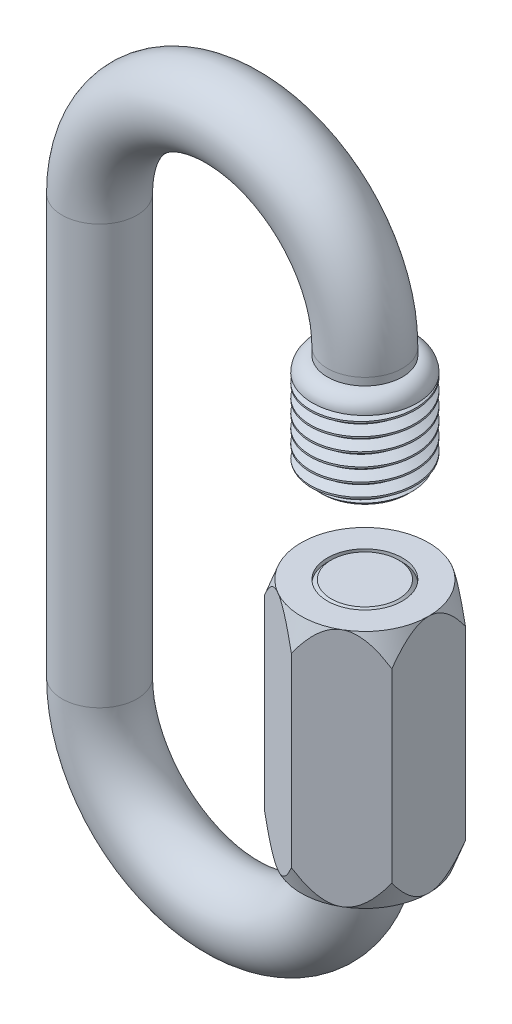
SolidWorks part; units mm, degrees
ref_plane "Front Plane" through (0, 0, 0) normal (0, 0, 1) x (1, 0, 0)
ref_plane "Top Plane" through (0, 0, 0) normal (0, 1, 0) x (1, 0, 0)
ref_plane "Right Plane" through (0, 0, 0) normal (1, 0, 0) x (0, 0, -1)
sketch "Sketch1" plane through (0, 0, 0) normal (0, 0, 1) x (1, 0, 0)
  line L0 (6.35, 13.97) -> (6.35, 13.47) construction
  line L1 (-11.35, 25.32) -> (11.35, 25.32) construction
  line L2 (-11.35, 25.32) -> (-11.35, -25.32) construction
  line L3 (-11.35, -25.32) -> (11.35, -25.32) construction
  line L4 (11.35, 25.32) -> (11.35, 13.97) construction
  line L5 (4.6, 0.53) -> (13.1, 0.53) construction
  line L6 (4.6, 0.53) -> (4.6, -15.47) construction
  line L7 (4.6, -15.47) -> (13.1, -15.47) construction
  line L8 (13.1, 0.53) -> (13.1, -15.47) construction
  line L9 (-11.35, 0) -> (-6.35, 0) construction
  line L10 (-6.35, -13.97) -> (-6.35, 13.97) construction
  line L11 (6.35, 0.53) -> (6.35, -13.97) construction
  line L12 (6.35, -13.97) -> (11.35, -13.97) construction
  line L13 (11.35, 0.53) -> (11.35, -25.32) construction
  line L14 (11.35, 13.97) -> (11.35, 13.47) construction
  line L15 (12.35, 13.47) -> (5.35, 13.47) construction
  line L16 (5.35, 13.47) -> (5.35, 6.88) construction
  line L17 (5.35, 6.88) -> (12.35, 6.88) construction
  line L18 (12.35, 6.88) -> (12.35, 13.47) construction
  line L19 (12.4447, 6.9347) -> (12.4447, 6.0597) construction
  line L20 (12.4447, 6.0597) -> (11.6869, 6.4972) construction
  line L21 (11.6869, 6.4972) -> (12.4447, 6.9347) construction
  line L22 (11.6869, 6.4972) -> (11.7817, 6.4972) construction
  line L23 (11.7817, 6.5519) -> (11.7817, 6.4425) construction
  line L24 (12.4447, 6.4972) -> (12.35, 6.4972) construction
  line L25 (12.35, 6.1144) -> (12.35, 6.88) construction
  line L26 (12.3974, 6.4972) -> (12.3974, 6.9073) construction
  line L27 (12.3974, 6.4972) -> (12.3974, 6.087) construction
  line L28 (11.6937, 6.88) -> (12.35, 7.5362) construction
  arc A0 (-11.35, 13.97) -> (11.35, 13.97) centre (0, 13.97) cw construction
  arc A1 (-11.35, -13.97) -> (11.35, -13.97) centre (0, -13.97) ccw construction
  arc A2 (6.35, 13.97) -> (-6.35, 13.97) centre (0, 13.97) ccw construction
  arc A3 (-6.35, -13.97) -> (6.35, -13.97) centre (0, -13.97) ccw construction
  arc A4 (11.35, 13.47) -> (12.35, 12.47) centre (11.35, 12.47) cw construction
  point P4 (-11.35, 0)
  point P5 (0, 25.32)
  point P21 (8.85, -13.97)
  point P22 (8.85, -15.47)
  point P28 (-6.35, -25.32)
  point P29 (6.35, -25.32)
  point P35 (8.85, 6.88)
  point P36 (8.85, 0.53)
  point P49 (-8.85, 0)
  point P54 (0, -20.32)
  point P55 (0, 20.32)
  point P56 (-11.35, 20.32)
  point P57 (-11.35, -20.32)
  dimension "Hex Flats" = 8.5
  dimension "Thickness" = 5
  dimension "Inside Length" = 40.64
  dimension "Inside Width" = 12.7
  dimension "Hex Length" = 16
  dimension "Opening Width" = 6.35
  dimension "Thread Diameter" = 7
  dimension "D3" = 0.5
  dimension "Pitch" = 0.875
  dimension "D4" = 0.1094
  dimension "D5" = 45
  dimension "D6" = 0.6563
  dimension "D1" = 6.59
ref_plane "Plane1" through (0, 13.47, 0) normal (0, 1, 0) x (1, 0, 0)
sketch "Sketch2" plane through (0, 0, 0) normal (0, 1, 0) x (1, 0, 0)
  circle A0 centre (-8.85, 0) radius 2.5
sketch "Sketch3" plane through (0, 0, 0) normal (0, 0, 1) x (1, 0, 0)
  line L0 (4.6, 0.53) -> (13.1, 0.53) construction
  line L1 (12.35, 13.47) -> (5.35, 13.47) construction
  line L2 (8.85, 13.47) -> (8.85, 6.88)
  line L3 (5.35, 6.88) -> (12.35, 6.88) construction
  line L21 (8.85, 0.53) -> (8.85, -13.97)
  line L22 (-8.85, -13.97) -> (-8.85, 13.97)
  line L23 (8.85, 13.97) -> (8.85, 13.47)
  arc A0 (-6.35, -13.97) -> (6.35, -13.97) centre (0, -13.97) ccw construction
  arc A1 (6.35, 13.97) -> (-6.35, 13.97) centre (0, 13.97) ccw construction
  arc A16 (-8.85, -13.97) -> (8.85, -13.97) centre (0, -13.97) ccw
  arc A17 (8.85, 13.97) -> (-8.85, 13.97) centre (0, 13.97) ccw
sweep "Sweep1" add profiles "Sketch2" path "Sketch3"
sketch "Sketch5" plane through (0, 0, 0) normal (0, 0, 1) x (1, 0, 0)
  line L0 (5.35, 6.88) -> (12.35, 6.88) construction
  line L1 (11.6937, 6.88) -> (12.35, 7.5362) construction
  line L2 (12.35, 6.88) -> (12.35, 13.47) construction
  line L3 (12.35, 13.47) -> (5.35, 13.47) construction
  line L4 (8.85, 6.88) -> (11.6937, 6.88)
  line L5 (11.6937, 6.88) -> (12.35, 7.5362)
  line L6 (12.35, 7.5362) -> (12.35, 12.47)
  line L7 (11.35, 13.47) -> (8.85, 13.47)
  line L8 (8.85, 6.88) -> (8.85, 13.47)
  arc A0 (12.35, 12.47) -> (11.35, 13.47) centre (11.35, 12.47) ccw construction
  arc A1 (12.35, 12.47) -> (11.35, 13.47) centre (11.35, 12.47) ccw
revolve "Revolve1" add sketch "Sketch5" angle 360 about L8
chamfer "Chamfer1" distance 0.254 angle 45 1 edges at (8.85, 0.53, 2.5)
sketch "Sketch6" plane through (0, 0, 0) normal (0, 1, 0) x (1, 0, 0)
  line L0 (6.35, 0) -> (11.35, 0) construction
  line L1 (13.1, -2.4537) -> (13.1, 2.4537)
  line L2 (13.1, 2.4537) -> (8.85, 4.9075)
  line L3 (8.85, 4.9075) -> (4.6, 2.4537)
  line L4 (4.6, 2.4537) -> (4.6, -2.4537)
  line L5 (4.6, -2.4537) -> (8.85, -4.9075)
  line L6 (8.85, -4.9075) -> (13.1, -2.4537)
  line L7 (6.35, 0) -> (11.35, 0) construction
  circle A0 centre (8.85, 0) radius 4.25 construction
  circle A1 centre (8.85, 0) radius 2.5
extrude "Boss-Extrude1" add sketch "Sketch6" against normal up to vertex (15.47 mm away) from vertex separate body up to point (4.6, -15.47, 0) starting at point (4.6, 0.53, 0)
sketch "Sketch7" plane through (0, 0.53, 0) normal (0, 1, 0) x (1, 0, 0)
  circle A0 centre (8.85, 0) radius 4.25 construction
  circle A1 centre (8.85, 0) radius 4.25
extrude "Cut-Extrude1" cut sketch "Sketch7" against normal through all draft 20 flip side to cut
sketch "Sketch8" plane through (0, -15.47, 0) normal (0, -1, 0) x (1, 0, 0)
  circle A1 centre (8.85, 0) radius 4.25
  circle A2 centre (8.85, 0) radius 4.25
  dimension "D1" = 0
extrude "Cut-Extrude2" cut sketch "Sketch8" against normal through all draft 20 flip side to cut
sketch "Sketch9" plane through (0, 6.88, 0) normal (0, -1, 0) x (1, 0, 0)
  circle A0 centre (8.85, 0) radius 3.5
curve "Helix/Spiral1" pitch 0.875 height 7.465 radius 3.5 centre (8.85, 6.88, 0) axis (0, 1, 0) start towards (1, 0, 0)
split "Split1" trim tools "Plane1" bodies to split 105 resulting bodies 111 112 113
sketch "Sketch11" plane through (0, 0, 0) normal (0, 0, 1) x (1, 0, 0)
  line L0 (12.3974, 6.9073) -> (11.7817, 6.5519)
  line L1 (11.7817, 6.5519) -> (11.7817, 6.4425)
  line L2 (11.7817, 6.4425) -> (12.3974, 6.087)
  line L3 (12.3974, 6.087) -> (12.3974, 6.9073)
sweep "Cut-Sweep1" cut profiles "Sketch11" path "Helix/Spiral1" align with end faces yes
sketch "Sketch12" plane through (0, 0, 0) normal (0, 0, 1) x (1, 0, 0)
  line L0 (11.35, 13.97) -> (11.35, 13.47)
  line L1 (11.35, 13.97) -> (8.85, 13.97)
  line L4 (8.85, 13.47) -> (8.85, 6.88) construction
  line L5 (5.35, 6.88) -> (12.35, 6.88) construction
  line L6 (12.35, 13.47) -> (5.35, 13.47) construction
  line L9 (6.35, 13.97) -> (11.35, 13.97) construction
  line L10 (8.85, 13.97) -> (8.85, 12.47)
  line L11 (8.85, 12.47) -> (12.35, 12.47)
  arc A0 (12.35, 12.47) -> (11.35, 13.47) centre (11.35, 12.47) ccw construction
  arc A1 (12.35, 12.47) -> (11.35, 13.47) centre (11.35, 12.47) ccw
revolve "Revolve2" add sketch "Sketch12" angle 360 about L4
equation "\"Hex Flats@Sketch1\" = \"Thickness@Sketch1\" * 1.7"
equation "\"D3@Sketch1\"=\"Thickness@Sketch1\"*.1"
equation "\"D4@Sketch1\"=\"Pitch@Sketch1\"/8"
equation "\"D6@Sketch1\"=\"Pitch@Sketch1\"*.75"
equation "\"D3@Helix/Spiral1\"=\"D1@Sketch1\"+\"Pitch@Sketch1\""
equation "\"D4@Helix/Spiral1\"=\"Pitch@Sketch1\""
equation "\"Pitch@Sketch1\"=\"Thread Diameter@Sketch1\"*.125"
equation "\"D1@Sketch1\"=\"Inside Length@Sketch1\"-\"Inside Width@Sketch1\"-\"Hex Length@Sketch1\"-\"Opening Width@Sketch1\"+(2*\"D3@Sketch1\")"
